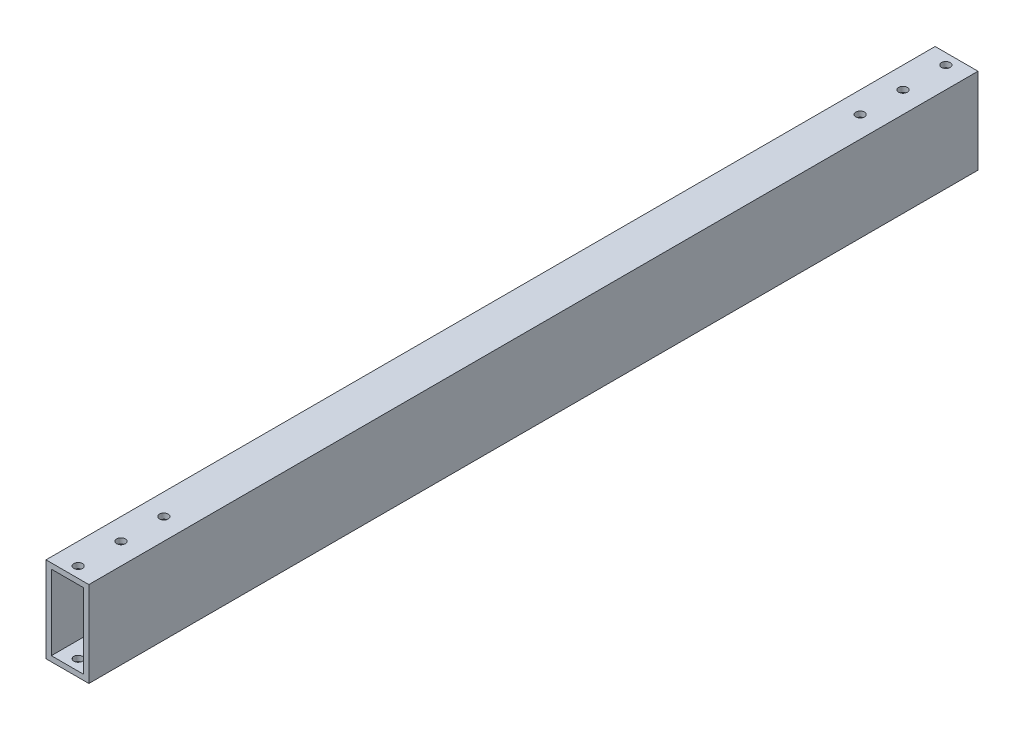
SolidWorks part; units mm, degrees
material "6061-T6 (SS)"
ref_plane "Front" through (0, 0, 0) normal (0, 0, 1) x (1, 0, 0)
ref_plane "Top" through (0, 0, 0) normal (0, 1, 0) x (1, 0, 0)
ref_plane "Right" through (0, 0, 0) normal (1, 0, 0) x (0, 0, -1)
sketch "Sketch1" plane through (0, 0, 0) normal (0, 0, 1) x (1, 0, 0)
  line L1 (-12.7, -25.4) -> (12.7, -25.4)
  line L2 (-12.7, -25.4) -> (-12.7, 25.4)
  line L3 (-12.7, 25.4) -> (12.7, 25.4)
  line L4 (12.7, -25.4) -> (12.7, 25.4)
  line L5 (-12.7, -25.4) -> (12.7, 25.4) construction
  line L6 (-12.7, 25.4) -> (12.7, -25.4) construction
  point P0 (0, 0)
  dimension "D1" = 25.4
  dimension "D2" = 50.8
extrude "Extrude-Thin1" add sketch "Sketch1" along normal blind 527.05 thin thin type one direction reverse wall 3.175
hole_wizard "#10 Clearance Hole1" positions "Sketch2" profile "Sketch3" hole size "#10" standard "ANSI Inch" end condition through all
sketch "Sketch2" plane through (0, 25.4, 0) normal (0, 1, 0) x (1, 0, 0)
  line L0 (12.7, -527.05) -> (-12.7, -527.05) construction
  line L1 (-12.7, -527.05) -> (-12.7, 0) construction
  point P0 (0, -520.7)
  point P2 (0, -495.3)
  point P4 (0, -469.9)
  point P6 (0, -6.35)
  point P8 (0, -31.75)
  point P10 (0, -57.15)
  dimension "D1" = 6.35
  dimension "D2" = 12.7
  dimension "D3" = 25.4
  dimension "D4" = 25.4
  dimension "D5" = 6.35
  dimension "D6" = 25.4
  dimension "D7" = 25.4
sketch "Sketch3" plane through (0, 25.4, 520.7) normal (1, 0, 0) x (0, 0, 1)
  line L0 (0, 0) -> (0, 50.8)
  line L1 (0, 50.8) -> (2.5527, 50.8)
  line L2 (2.5527, 50.8) -> (2.5527, 0)
  line L5 (2.5527, 0) -> (0, 0)
  line L11 (0, -6.35) -> (0, 107.95) construction
  dimension "Thru Hole Dia." = 5.1054
  dimension "Thru Hole Depth" = 50.8
